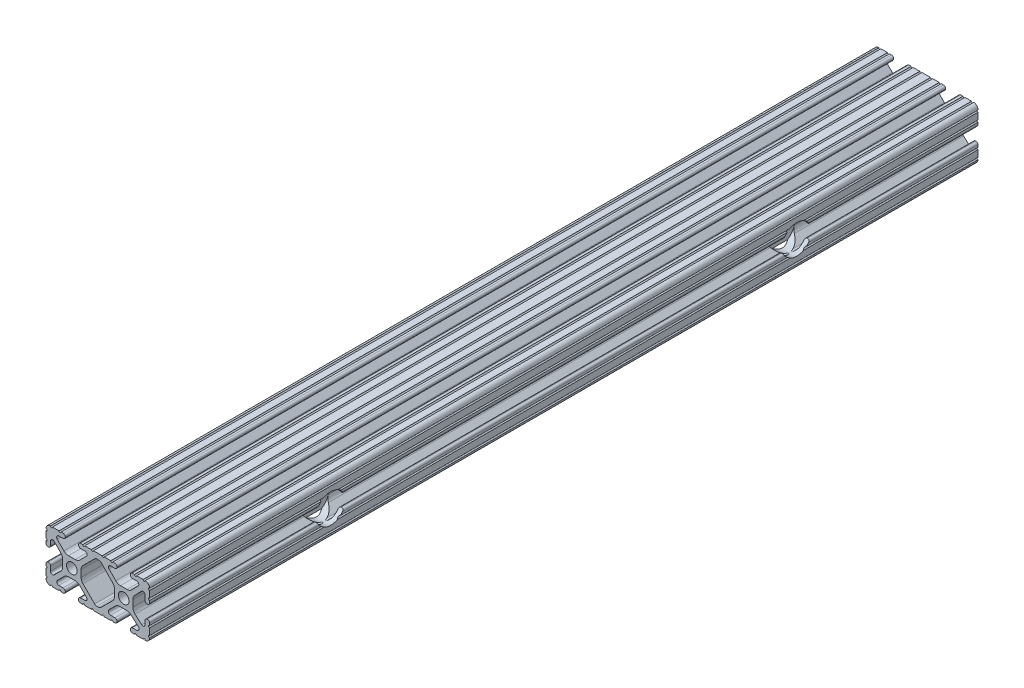
SolidWorks part; units mm, degrees
ref_plane "Front Plane" through (0, 0, 0) normal (0, 0, 1) x (1, 0, 0)
ref_plane "Top Plane" through (0, 0, 0) normal (0, 1, 0) x (1, 0, 0)
ref_plane "Right Plane" through (0, 0, 0) normal (1, 0, 0) x (0, 0, -1)
sketch "Sketch1" plane through (0, 0, 0) normal (0, 0, 1) x (1, 0, 0)
  line L0 (-7.2595, -3.8694) -> (-1.5457, -9.5728)
  line L1 (-8.1915, 1.6223) -> (-8.1915, -1.6223)
  line L2 (-1.504, 9.5765) -> (-7.252, 3.8768)
  line L3 (0.5515, 10.033) -> (-0.3952, 10.033)
  line L4 (7.2829, 3.8459) -> (1.6756, 9.5611)
  line L5 (8.1915, -1.6223) -> (8.1915, 1.6223)
  line L6 (1.5457, -9.5728) -> (7.2595, -3.8694)
  line L7 (-0.4332, -10.033) -> (0.4332, -10.033)
  line L8 (18.0171, 12.7) -> (16.9875, 12.7)
  line L9 (15.9385, 11.651) -> (15.9385, 11.5392)
  line L10 (16.9875, 10.4902) -> (19.1164, 10.4902)
  line L11 (19.8441, 8.7652) -> (16.619, 5.4551)
  line L12 (14.3449, 4.4958) -> (11.0833, 4.4958)
  line L13 (8.817, 5.4472) -> (5.5642, 8.7627)
  line L14 (6.2894, 10.4902) -> (8.4125, 10.4902)
  line L15 (9.4615, 11.5392) -> (9.4615, 11.651)
  line L16 (8.4125, 12.7) -> (7.3829, 12.7)
  line L17 (6.3669, 12.7) -> (3.1496, 12.7)
  line L18 (2.1336, 12.7) -> (-2.1336, 12.7)
  line L19 (-3.1496, 12.7) -> (-6.3669, 12.7)
  line L20 (-7.3829, 12.7) -> (-8.4125, 12.7)
  line L21 (-9.4615, 11.651) -> (-9.4615, 11.5392)
  line L22 (-8.4125, 10.4902) -> (-6.2836, 10.4902)
  line L23 (-5.5326, 8.6661) -> (-8.81, 5.4163)
  line L24 (-11.0455, 4.4958) -> (-14.3545, 4.4958)
  line L25 (-16.59, 5.4163) -> (-19.8674, 8.6661)
  line L26 (-19.1164, 10.4902) -> (-16.9875, 10.4902)
  line L27 (-15.9385, 11.5392) -> (-15.9385, 11.651)
  line L28 (-16.9875, 12.7) -> (-18.0171, 12.7)
  line L29 (-19.0331, 12.7) -> (-22.2504, 12.7)
  line L30 (-25.4, 9.5504) -> (-25.4, 6.3331)
  line L31 (-25.4, 5.3171) -> (-25.4, 4.2375)
  line L32 (-24.401, 3.2385) -> (-24.2392, 3.2385)
  line L33 (-23.1902, 4.2875) -> (-23.1902, 6.3347)
  line L34 (-21.434, 7.0665) -> (-18.148, 3.8082)
  line L35 (-17.2085, 1.5536) -> (-17.2085, -1.6952)
  line L36 (-18.1405, -3.9423) -> (-21.4316, -7.2274)
  line L37 (-23.1902, -6.498) -> (-23.1902, -4.2875)
  line L38 (-24.2392, -3.2385) -> (-24.351, -3.2385)
  line L39 (-25.4, -4.2875) -> (-25.4, -5.3171)
  line L40 (-25.4, -6.3331) -> (-25.4, -9.5504)
  line L41 (-22.2504, -12.7) -> (-19.0331, -12.7)
  line L42 (-18.0171, -12.7) -> (-16.9875, -12.7)
  line L43 (-15.9384, -11.651) -> (-15.9384, -11.5392)
  line L44 (-16.9875, -10.4902) -> (-19.1164, -10.4902)
  line L45 (-19.8341, -8.7551) -> (-16.4966, -5.4237)
  line L46 (-14.2536, -4.4958) -> (-11.1464, -4.4958)
  line L47 (-8.9034, -5.4237) -> (-5.5659, -8.7551)
  line L48 (-6.2836, -10.4902) -> (-8.4125, -10.4902)
  line L49 (-9.4616, -11.5392) -> (-9.4616, -11.651)
  line L50 (-8.4125, -12.7) -> (-7.3829, -12.7)
  line L51 (-6.3669, -12.7) -> (-3.1496, -12.7)
  line L52 (-2.1336, -12.7) -> (2.1336, -12.7)
  line L53 (3.1496, -12.7) -> (6.3669, -12.7)
  line L54 (7.3829, -12.7) -> (8.4125, -12.7)
  line L55 (9.4616, -11.651) -> (9.4616, -11.5392)
  line L56 (8.4125, -10.4902) -> (6.2894, -10.4902)
  line L57 (5.4807, -8.5353) -> (8.5979, -5.4237)
  line L58 (10.8409, -4.4958) -> (14.1026, -4.4958)
  line L59 (16.1879, -5.2766) -> (19.8682, -8.4822)
  line L60 (19.1164, -10.4902) -> (16.9875, -10.4902)
  line L61 (15.9384, -11.5392) -> (15.9384, -11.651)
  line L62 (16.9875, -12.7) -> (18.0171, -12.7)
  line L63 (19.0331, -12.7) -> (22.2504, -12.7)
  line L64 (25.4, -9.5504) -> (25.4, -6.3331)
  line L65 (25.4, -5.3171) -> (25.4, -4.2375)
  line L66 (24.401, -3.2385) -> (24.1892, -3.2385)
  line L67 (23.1902, -4.2375) -> (23.1902, -6.1559)
  line L68 (21.584, -6.8869) -> (18.2982, -4.025)
  line L69 (17.2085, -1.6308) -> (17.2085, 1.6308)
  line L70 (18.1094, 3.8465) -> (21.5263, 7.3534)
  line L71 (23.1902, 6.6769) -> (23.1902, 4.2375)
  line L72 (24.1892, 3.2385) -> (24.401, 3.2385)
  line L73 (25.4, 4.2375) -> (25.4, 5.3171)
  line L74 (25.4, 6.3332) -> (25.4, 9.5504)
  line L75 (22.2504, 12.7) -> (19.0331, 12.7)
  circle A0 centre (-12.7, 0) radius 2.6035
  circle A1 centre (12.7, 0) radius 2.6035
  arc A2 (-1.5457, -9.5728) -> (-0.4332, -10.033) centre (-0.4332, -8.4582) ccw
  arc A3 (-8.1915, -1.6223) -> (-7.2595, -3.8694) centre (-5.0165, -1.6223) ccw
  arc A4 (-7.252, 3.8768) -> (-8.1915, 1.6223) centre (-5.0165, 1.6223) ccw
  arc A5 (-0.3952, 10.033) -> (-1.504, 9.5765) centre (-0.3952, 8.4582) ccw
  arc A6 (1.6756, 9.5611) -> (0.5515, 10.033) centre (0.5515, 8.4582) ccw
  arc A7 (8.1915, 1.6223) -> (7.2829, 3.8459) centre (5.0165, 1.6223) ccw
  arc A8 (7.2595, -3.8694) -> (8.1915, -1.6223) centre (5.0165, -1.6223) ccw
  arc A9 (0.4332, -10.033) -> (1.5457, -9.5728) centre (0.4332, -8.4582) ccw
  arc A10 (18.0171, 12.7) -> (19.0331, 12.7) centre (18.5251, 12.7) ccw
  arc A11 (16.9875, 12.7) -> (15.9385, 11.651) centre (16.9875, 11.651) ccw
  arc A12 (15.9385, 11.5392) -> (16.9875, 10.4902) centre (16.9875, 11.5392) ccw
  arc A13 (19.8441, 8.7652) -> (19.1164, 10.4902) centre (19.1164, 9.4742) ccw
  arc A14 (14.3449, 4.4958) -> (16.619, 5.4551) centre (14.3449, 7.6708) ccw
  arc A15 (8.817, 5.4472) -> (11.0833, 4.4958) centre (11.0833, 7.6708) ccw
  arc A16 (6.2894, 10.4902) -> (5.5642, 8.7627) centre (6.2894, 9.4742) ccw
  arc A17 (8.4125, 10.4902) -> (9.4615, 11.5392) centre (8.4125, 11.5392) ccw
  arc A18 (9.4615, 11.651) -> (8.4125, 12.7) centre (8.4125, 11.651) ccw
  arc A19 (6.3669, 12.7) -> (7.3829, 12.7) centre (6.8749, 12.7) ccw
  arc A20 (2.1336, 12.7) -> (3.1496, 12.7) centre (2.6416, 12.7) ccw
  arc A21 (-3.1496, 12.7) -> (-2.1336, 12.7) centre (-2.6416, 12.7) ccw
  arc A22 (-7.3829, 12.7) -> (-6.3669, 12.7) centre (-6.8749, 12.7) ccw
  arc A23 (-8.4125, 12.7) -> (-9.4615, 11.651) centre (-8.4125, 11.651) ccw
  arc A24 (-9.4615, 11.5392) -> (-8.4125, 10.4902) centre (-8.4125, 11.5392) ccw
  arc A25 (-5.5326, 8.6661) -> (-6.2836, 10.4902) centre (-6.2836, 9.4235) ccw
  arc A26 (-11.0455, 4.4958) -> (-8.81, 5.4163) centre (-11.0455, 7.6708) ccw
  arc A27 (-16.59, 5.4163) -> (-14.3545, 4.4958) centre (-14.3545, 7.6708) ccw
  arc A28 (-19.1164, 10.4902) -> (-19.8674, 8.6661) centre (-19.1164, 9.4235) ccw
  arc A29 (-16.9875, 10.4902) -> (-15.9385, 11.5392) centre (-16.9875, 11.5392) ccw
  arc A30 (-15.9385, 11.651) -> (-16.9875, 12.7) centre (-16.9875, 11.651) ccw
  arc A31 (-19.0331, 12.7) -> (-18.0171, 12.7) centre (-18.5251, 12.7) ccw
  arc A32 (-23.2664, 12.6998) -> (-22.2504, 12.7) centre (-22.7584, 12.7) ccw
  arc A33 (-23.2664, 12.6998) -> (-25.3998, 10.5664) centre (-23.2918, 10.5918) ccw
  arc A34 (-25.4, 9.5504) -> (-25.3998, 10.5664) centre (-25.4, 10.0584) ccw
  arc A35 (-25.4, 5.3171) -> (-25.4, 6.3331) centre (-25.4, 5.8251) ccw
  arc A36 (-25.4, 4.2375) -> (-24.401, 3.2385) centre (-24.401, 4.2375) ccw
  arc A37 (-24.2392, 3.2385) -> (-23.1902, 4.2875) centre (-24.2392, 4.2875) ccw
  arc A38 (-21.434, 7.0665) -> (-23.1902, 6.3347) centre (-22.1596, 6.3347) ccw
  arc A39 (-17.2085, 1.5536) -> (-18.148, 3.8082) centre (-20.3835, 1.5536) ccw
  arc A40 (-18.1405, -3.9423) -> (-17.2085, -1.6952) centre (-20.3835, -1.6952) ccw
  arc A41 (-23.1902, -6.498) -> (-21.4316, -7.2274) centre (-22.1596, -6.498) ccw
  arc A42 (-23.1902, -4.2875) -> (-24.2392, -3.2385) centre (-24.2392, -4.2875) ccw
  arc A43 (-24.351, -3.2385) -> (-25.4, -4.2875) centre (-24.351, -4.2875) ccw
  arc A44 (-25.4, -6.3331) -> (-25.4, -5.3171) centre (-25.4, -5.8251) ccw
  arc A45 (-25.3998, -10.5664) -> (-25.4, -9.5504) centre (-25.4, -10.0584) ccw
  arc A46 (-25.3998, -10.5664) -> (-23.2664, -12.6998) centre (-23.2918, -10.5918) ccw
  arc A47 (-22.2504, -12.7) -> (-23.2664, -12.6998) centre (-22.7584, -12.7) ccw
  arc A48 (-18.0171, -12.7) -> (-19.0331, -12.7) centre (-18.5251, -12.7) ccw
  arc A49 (-16.9875, -12.7) -> (-15.9384, -11.651) centre (-16.9875, -11.651) ccw
  arc A50 (-15.9384, -11.5392) -> (-16.9875, -10.4902) centre (-16.9875, -11.5392) ccw
  arc A51 (-19.8341, -8.7551) -> (-19.1164, -10.4902) centre (-19.1164, -9.4742) ccw
  arc A52 (-14.2536, -4.4958) -> (-16.4966, -5.4237) centre (-14.2536, -7.6708) ccw
  arc A53 (-8.9034, -5.4237) -> (-11.1464, -4.4958) centre (-11.1464, -7.6708) ccw
  arc A54 (-6.2836, -10.4902) -> (-5.5659, -8.7551) centre (-6.2836, -9.4742) ccw
  arc A55 (-8.4125, -10.4902) -> (-9.4616, -11.5392) centre (-8.4125, -11.5392) ccw
  arc A56 (-9.4616, -11.651) -> (-8.4125, -12.7) centre (-8.4125, -11.651) ccw
  arc A57 (-6.3669, -12.7) -> (-7.3829, -12.7) centre (-6.8749, -12.7) ccw
  arc A58 (-2.1336, -12.7) -> (-3.1496, -12.7) centre (-2.6416, -12.7) ccw
  arc A59 (3.1496, -12.7) -> (2.1336, -12.7) centre (2.6416, -12.7) ccw
  arc A60 (7.3829, -12.7) -> (6.3669, -12.7) centre (6.8749, -12.7) ccw
  arc A61 (8.4125, -12.7) -> (9.4616, -11.651) centre (8.4125, -11.651) ccw
  arc A62 (9.4616, -11.5392) -> (8.4125, -10.4902) centre (8.4125, -11.5392) ccw
  arc A63 (5.4807, -8.5353) -> (6.2894, -10.4902) centre (6.2894, -9.3455) ccw
  arc A64 (10.8409, -4.4958) -> (8.5979, -5.4237) centre (10.8409, -7.6708) ccw
  arc A65 (16.1879, -5.2766) -> (14.1026, -4.4958) centre (14.1026, -7.6708) ccw
  arc A66 (19.1164, -10.4902) -> (19.8682, -8.4822) centre (19.1164, -9.3455) ccw
  arc A67 (16.9875, -10.4902) -> (15.9384, -11.5392) centre (16.9875, -11.5392) ccw
  arc A68 (15.9384, -11.651) -> (16.9875, -12.7) centre (16.9875, -11.651) ccw
  arc A69 (19.0331, -12.7) -> (18.0171, -12.7) centre (18.5251, -12.7) ccw
  arc A70 (23.2664, -12.6998) -> (22.2504, -12.7) centre (22.7584, -12.7) ccw
  arc A71 (23.2664, -12.6998) -> (25.3998, -10.5664) centre (23.2918, -10.5918) ccw
  arc A72 (25.4, -9.5504) -> (25.3998, -10.5664) centre (25.4, -10.0584) ccw
  arc A73 (25.4, -5.3171) -> (25.4, -6.3331) centre (25.4, -5.8251) ccw
  arc A74 (25.4, -4.2375) -> (24.401, -3.2385) centre (24.401, -4.2375) ccw
  arc A75 (24.1892, -3.2385) -> (23.1902, -4.2375) centre (24.1892, -4.2375) ccw
  arc A76 (21.584, -6.8869) -> (23.1902, -6.1559) centre (22.2207, -6.1559) ccw
  arc A77 (17.2085, -1.6308) -> (18.2982, -4.025) centre (20.3835, -1.6308) ccw
  arc A78 (18.1094, 3.8465) -> (17.2085, 1.6308) centre (20.3835, 1.6308) ccw
  arc A79 (23.1902, 6.6769) -> (21.5263, 7.3534) centre (22.2207, 6.6769) ccw
  arc A80 (23.1902, 4.2375) -> (24.1892, 3.2385) centre (24.1892, 4.2375) ccw
  arc A81 (24.401, 3.2385) -> (25.4, 4.2375) centre (24.401, 4.2375) ccw
  arc A82 (25.4, 6.3332) -> (25.4, 5.3171) centre (25.4, 5.8251) ccw
  arc A83 (25.3998, 10.5664) -> (25.4, 9.5504) centre (25.4, 10.0584) ccw
  arc A84 (25.3998, 10.5664) -> (23.2664, 12.6998) centre (23.2918, 10.5918) ccw
  arc A85 (22.2504, 12.7) -> (23.2664, 12.6998) centre (22.7584, 12.7) ccw
  point P248 (0, 10.033)
extrude "Boss-Extrude1" add sketch "Sketch1" along normal mid plane 406.4
hole_wizard "CBORE for 1/4 Binding Head Machine Screw1" positions "Sketch4" profile "Sketch6" counterbore size "1/4" standard "ANSI Inch" end condition through all
sketch "Sketch4" plane through (25.4, 0, 0) normal (1, 0, 0) x (0, 0, -1)
  line L0 (-114.3, 0) -> (114.3, 0) construction
  point P0 (-114.3, 0)
  point P2 (114.3, 0)
  point P9 (0, 0)
  dimension "D1" = 228.6
sketch "Sketch6" plane through (25.4, 0, 114.3) normal (0, 1, 0) x (0, 0, -1)
  line L0 (0, 0) -> (0, 50.8)
  line L1 (0, 50.8) -> (3.3782, 50.8)
  line L3 (3.3782, 50.8) -> (3.3782, 8.255)
  line L4 (3.3782, 8.255) -> (7.1437, 8.255)
  line L5 (7.1437, 8.255) -> (7.1437, 0)
  line L7 (7.1437, 0) -> (0, 0)
  line L11 (0, -6.35) -> (0, 107.95) construction
  dimension "Thru Hole Dia." = 6.7564
  dimension "Thru Hole Depth" = 50.8
  dimension "C'Bore Dia." = 14.2875
  dimension "C'Bore Depth" = 8.255
hole_wizard "1/4 (0.25) Diameter Hole1" positions "Sketch7" profile "Sketch9" hole size "1/4" standard "ANSI Inch" end condition through all
sketch "Sketch7" plane through (25.4, 0, 0) normal (1, 0, 0) x (0, 0, -1)
  line L0 (-76.2, 0) -> (76.2, 0) construction
  point P0 (-76.2, 0)
  point P2 (76.2, 0)
  point P10 (0, 0)
  dimension "D1" = 152.4
sketch "Sketch9" plane through (25.4, 0, 76.2) normal (0, 1, 0) x (0, 0, -1)
  line L0 (0, 0) -> (0, 50.8)
  line L1 (0, 50.8) -> (3.175, 50.8)
  line L2 (3.175, 50.8) -> (3.175, 0)
  line L5 (3.175, 0) -> (0, 0)
  line L11 (0, -6.35) -> (0, 107.95) construction
  dimension "Thru Hole Dia." = 6.35
  dimension "Thru Hole Depth" = 50.8
